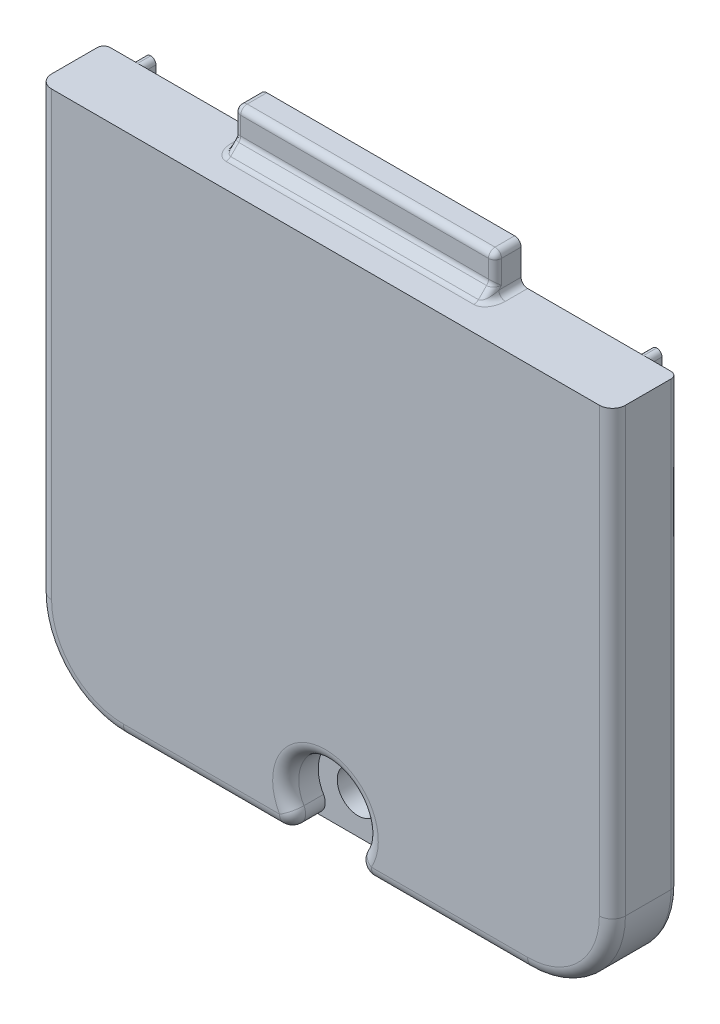
SolidWorks part; units mm, degrees
note: The reader was unsure of these and kept them because the rebuilt part matched: shared geometry of "Эскиз2<4>", "Эскиз3<4>".
material "ABS"
ref_plane "Спереди" through (0, 0, 0) normal (0, 0, 1) x (1, 0, 0)
ref_plane "Сверху" through (0, 0, 0) normal (0, 1, 0) x (1, 0, 0)
ref_plane "Справа" through (0, 0, 0) normal (1, 0, 0) x (0, 0, -1)
sketch "Эскиз1" plane through (0, 0, 0) normal (0, 0, 1) x (1, 0, 0)
  line L0 (0, 38.9856) -> (0, -23.2968) construction
  line L1 (-22, 15.414) -> (22, 15.414)
  line L2 (22, 15.414) -> (22, -25)
  line L3 (22, -25) -> (-22, -25)
  line L4 (-22, -25) -> (-22, 15.414)
  line L5 (-17.7358, 31.2294) -> (-5.7489, -2.0695) construction
  line L6 (-5.7489, -2.0695) -> (-5.6214, -1.9266)
  line L7 (5.7489, -2.0695) -> (17.7358, 31.2294) construction
  arc A0 (-5.7489, -2.0695) -> (5.7489, -2.0695) centre (0, 0) ccw construction
  arc A1 (17.7358, 31.2294) -> (-17.7358, 31.2294) centre (0, 37.614) ccw construction
  point P6 (0, 15.414)
  dimension "D1" = 6.11
  dimension "D2" = 18.85
  dimension "D3" = 158
  dimension "D4" = 22.2
  dimension "D5" = 25
  dimension "D6" = 44
extrude "Бобышка-Вытянуть1" add sketch "Эскиз1" along normal blind 5
fillet "Скругление1" radius 6.5 2 edges at (-22, -25, 2.5) (22, -25, 2.5)
sketch "Эскиз2" plane through (0, 0, 5) normal (0, 0, 1) x (1, 0, 0)
  line L1 (0, 4.32) -> (0, -6.5599) construction
  line L2 (15.5, -25) -> (-15.5, -25) construction
  circle A0 centre (0, -22) radius 3.05
  circle A1 centre (0, -22) radius 1.6
  dimension "D1" = 6.1
  dimension "D2" = 3.2
  dimension "D3" = 3
extrude "Вырез-Вытянуть2" cut sketch "Эскиз2" against normal blind 2.5 contours A0
extrude "Вырез-Вытянуть3" cut sketch "Эскиз2<4>" against normal through all contours A1
sketch "Эскиз2<4>" plane through (0, 0, 5) normal (0, 0, 1) x (1, 0, 0) same geometry as "Эскиз2"
fillet "Скругление2" radius 1 2 edges at (0.55, -25, 3.75) (-0.55, -25, 3.75)
fillet "Скругление3" radius 1 9 edges at (22, -1.543, 5) (20.0962, -23.0962, 5) (9.5109, -25, 5) (2.6575, -24.5031, 5) (-22, -1.543, 5) (-20.0962, -23.0962, 5) (-9.5109, -25, 5) (-2.6575, -24.5031, 5) (0, -18.95, 5)
sketch "Эскиз3" plane through (0, 0, 0) normal (0, 0, -1) x (-1, 0, 0)
  line L0 (-15.5, -22) -> (-4.899, -22)
  line L1 (-19, -18.5) -> (-19, 13.414)
  line L2 (-19, 13.414) -> (-1, 13.414)
  line L3 (19, 13.414) -> (19, -18.5)
  line L4 (22, 15.414) -> (-22, 15.414) construction
  line L5 (-19, 13.414) -> (-19, 15.414)
  line L6 (-19, 15.414) -> (-19.8, 15.414)
  line L7 (-19.8, 15.414) -> (-19.8, -18.5)
  line L8 (-15.5, -22.8) -> (-4.899, -22.8)
  line L9 (19, 13.414) -> (19, 15.414)
  line L10 (19, 15.414) -> (19.8, 15.414)
  line L11 (19.8, 15.414) -> (19.8, -18.5)
  line L12 (-13.1446, -23) -> (-2.4886, -23) construction
  line L13 (-15.5, -25) -> (15.5, -25) construction
  line L14 (0, -5.9294) -> (0, 6.3868) construction
  line L15 (13.1446, -23) -> (2.4886, -23) construction
  line L16 (4.899, -22) -> (15.5, -22)
  line L17 (-1, 13.414) -> (-1, -3.793)
  line L18 (4.899, -22.8) -> (15.5, -22.8)
  line L19 (1, 13.414) -> (1, -3.793)
  line L20 (1, 13.414) -> (19, 13.414)
  line L21 (-10.4941, -25) -> (-10.4941, 15.414) construction
  line L22 (-22, -4.793) -> (22, -4.793) construction
  line L23 (-22, 15.414) -> (-22, -18.5) construction
  line L24 (22, -18.5) -> (22, 15.414) construction
  line L25 (-19, -3.793) -> (-1, -3.793)
  line L26 (19, -5.793) -> (1, -5.793)
  line L27 (-15.8136, -5.793) -> (-15.8136, -3.793) construction
  line L28 (-1, -5.793) -> (-1, -18.127)
  line L29 (1, -5.793) -> (1, -18.127)
  line L30 (-1, -5.793) -> (-19, -5.793)
  line L31 (1, -3.793) -> (19, -3.793)
  arc A0 (-19, -18.5) -> (-15.5, -22) centre (-15.5, -18.5) ccw
  arc A1 (19, -18.5) -> (15.5, -22) centre (15.5, -18.5) cw
  arc A2 (-22, -18.5) -> (-15.5, -25) centre (-15.5, -18.5) ccw construction
  arc A3 (-19.8, -18.5) -> (-15.5, -22.8) centre (-15.5, -18.5) ccw
  arc A4 (15.5, -22.8) -> (19.8, -18.5) centre (15.5, -18.5) ccw
  circle A5 centre (0, -22) radius 1.6 construction
  circle A8 centre (0, -22) radius 3 construction
  arc A9 (3.1353, -21.36) -> (-3.1353, -21.36) centre (0, -22) ccw
  arc A10 (-4.899, -23) -> (-2.9394, -21.4) centre (-4.899, -21) ccw construction
  arc A11 (-4.899, -22.8) -> (-3.1353, -21.36) centre (-4.899, -21) ccw
  arc A12 (-4.899, -22) -> (-3.9192, -21.2) centre (-4.899, -21) ccw
  arc A13 (4.899, -23) -> (2.9394, -21.4) centre (4.899, -21) cw construction
  arc A14 (4.899, -22.8) -> (3.1353, -21.36) centre (4.899, -21) cw
  arc A15 (4.899, -22) -> (3.9192, -21.2) centre (4.899, -21) cw
  arc A16 (3.9192, -21.2) -> (-3.9192, -21.2) centre (0, -22) ccw
  point P58 (-10.4941, -4.793)
  point P71 (-15.8136, -4.793)
  line M24 (22, 15.414) -> (-22, 15.414)
  dimension "D1" = 3
  dimension "D4" = 4
  dimension "D5" = 6
  dimension "D6" = 0.8
  dimension "D8" = 2
  dimension "D2" = 2
  dimension "D3" = 0.8
  dimension "D7" = 2
  dimension "D9" = 2
  dimension "D10" = 2
extrude "Вырез-Вытянуть4" cut sketch "Эскиз3" against normal blind 2.4 contours L1 L25 L17 L2 | A16 L28 L30 L1 A0 L0 A12 | A16 A15 L16 A1 L3 L26 L29 | L19 L31 L3 L20
extrude "Бобышка-Вытянуть2" add sketch "Эскиз3<4>" along normal blind 1 contours A15 A16 A12 L0 A0 L1 L5 L7 A3 L8 A11 A9 A14 L18 A4 L11 L9 L3 A1 L16 M24
sketch "Эскиз3<4>" plane through (0, 0, 0) normal (0, 0, -1) x (-1, 0, 0) same geometry as "Эскиз3"
chamfer "Фаска1" distance 2.4 angle 45 12 edges at (19, 4.8105, 2.4) (10, 13.414, 2.4) (-10, 13.414, 2.4) (-19, 4.8105, 2.4) (-19, -12.1465, 2.4) (-17.9749, -20.9749, 2.4) (-10.1995, -22, 2.4) (-2.9001, -19.2451, 2.4) (19, -12.1465, 2.4) (17.9749, -20.9749, 2.4) (10.1995, -22, 2.4) (2.9001, -19.2451, 2.4) tangent propagation no
fillet "Скругление4" radius 1 16 edges at (-1, -5.793, 1.2) (-1, -3.793, 1.2) (1, -3.793, 1.2) (1, -5.793, 1.2) (-1, 12.214, 1.2) (1, 12.214, 1.2)
sketch "Эскиз4" plane through (0, 0, 0) normal (1, 0, 0) x (0, 0, -1)
  line L0 (0, 15.414) -> (0, 18.414)
  line L1 (0, 18.414) -> (-2, 18.414)
  line L2 (-2, 18.414) -> (-2, 16.3312)
  line L3 (-2, 16.3312) -> (-2.9172, 15.414)
  line L4 (-4, 15.414) -> (0, 15.414) construction
  line L5 (-2.9172, 15.414) -> (0, 15.414)
  line L6 (-5.0366, 15.614) -> (-3, 15.614) construction
  line L7 (-3, 15.614) -> (-1.9279, 16.6861) construction
  line L8 (0, 15.414) -> (0, -18.5) construction
  dimension "D1" = 0.2
  dimension "D3" = 3
  dimension "D4" = 2
  dimension "D5" = 0.2
  dimension "D6" = 135
  dimension "D7" = 3
extrude "Бобышка-Вытянуть3" add sketch "Эскиз4" along normal mid plane 20
fillet "Скругление5" radius 0.5 10 edges at (10, 15.8726, 2.4586) (0, 15.414, 2.9172) (10, 17.3726, 2) (-10, 15.8726, 2.4586) (-10, 17.3726, 2) (0, 18.414, 2) (-10, 18.414, 1) (10, 18.414, 1)
fillet "Скругление6" radius 0.5 3 edges at (9.8536, 16.2705, 1.8536) (-9.8536, 16.2705, 1.8536) (0, 16.3312, 2)
fillet "Скругление7" radius 0.4 4 edges
fillet "Скругление8" radius 0.5 5 edges at (-22, -1.543, 0) (-20.0962, -23.0962, 0) (0, -25, 0) (20.0962, -23.0962, 0) (22, -1.543, 0)
